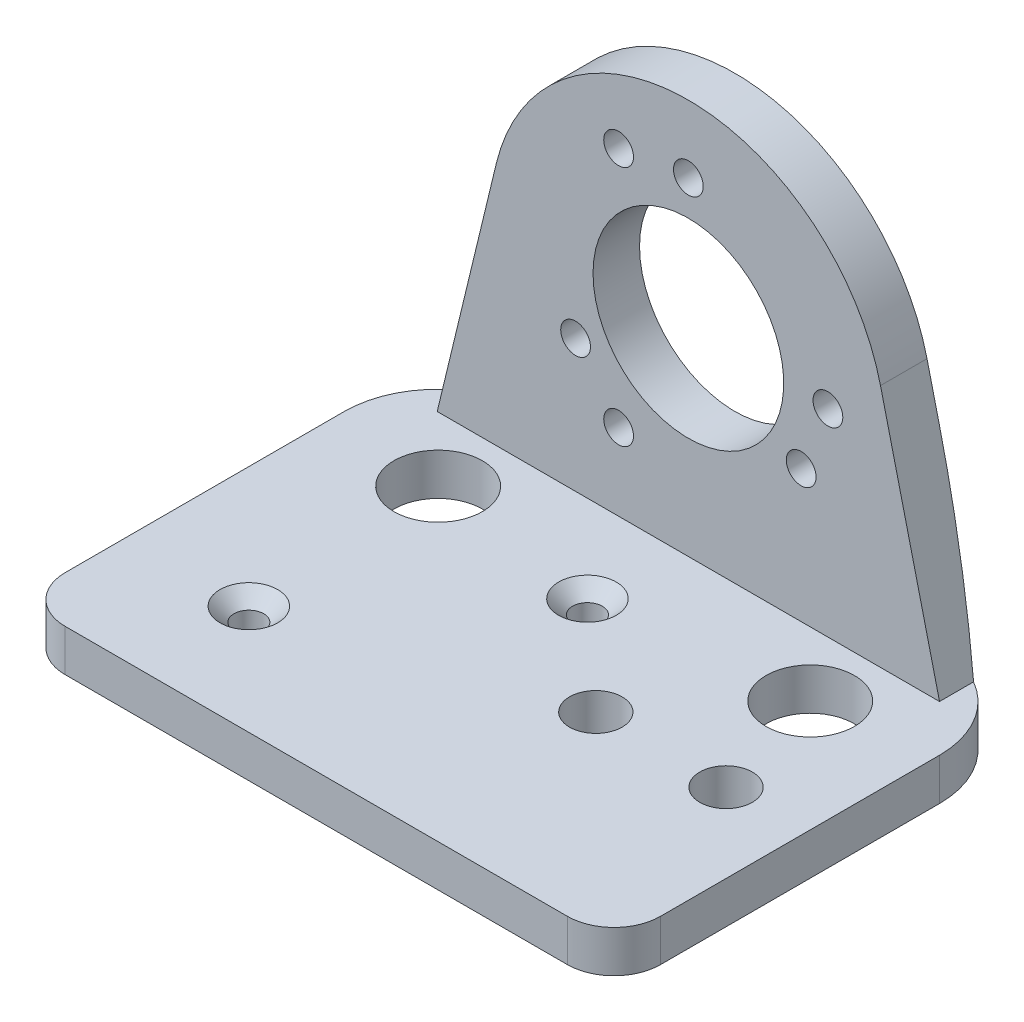
SolidWorks part; units mm, degrees
ref_plane "Front Plane" through (0, 0, 0) normal (0, 0, 1) x (1, 0, 0)
ref_plane "Top Plane" through (0, 0, 0) normal (0, 1, 0) x (1, 0, 0)
ref_plane "Right Plane" through (0, 0, 0) normal (1, 0, 0) x (0, 0, -1)
sketch "Sketch1" plane through (0, 0, 0) normal (0, 1, 0) x (1, 0, 0)
  line L0 (6.875, -1.95) -> (26.125, -1.95) construction
  line L1 (12.125, -1.95) -> (20.875, -1.95) construction
  line L2 (-32, -22.5) -> (32, -22.5)
  line L3 (32, -22.5) -> (32, 22.5)
  line L6 (-32, -22.5) -> (-32, 22.5)
  line L7 (-32, 22.5) -> (32, 22.5)
  line L9 (-32, 22.5) -> (32, -22.5) construction
  line L10 (32, 22.5) -> (-32, -22.5) construction
  line L11 (-20, 10.6) -> (0, 0) construction
  line L12 (0, 0) -> (20, 10.6) construction
  circle A0 centre (9.5, -1.95) radius 2.625 construction
  circle A1 centre (23.5, -1.95) radius 2.625 construction
  circle A2 centre (-1.5, 8.15) radius 1.6
  circle A3 centre (-19, -10.75) radius 1.6
  circle A4 centre (9.5, -1.95) radius 1.6 construction
  circle A5 centre (23.5, -1.95) radius 1.6 construction
  circle A7 centre (9.5, -1.95) radius 2.825
  circle A8 centre (23.5, -1.95) radius 2.825
  circle A9 centre (-20, 10.6) radius 4.75
  circle A10 centre (20, 10.6) radius 4.75
  point P19 (0, 0)
  dimension "D15" = 9.5
  dimension "D1" = 19.25
  dimension "D2" = 8.75
  dimension "D3" = 17.5
  dimension "D4" = 18.9
  dimension "D5" = 10.1
  dimension "D6" = 11
  dimension "D14" = 0.2
  dimension "D10" = 64
  dimension "D11" = 45
  dimension "D7" = 9.5
  dimension "D9" = 1.95
  dimension "D12" = 40
  dimension "D13" = 10.6
extrude "Boss-Extrude1" add sketch "Sketch1" against normal blind 4.5
chamfer "Chamfer1" distance 1.5 angle 45 2 edges at (-19, 0, 12.35) (-1.5, 0, -6.55)
sketch "Sketch2" plane through (0, 0, 0) normal (0, 0, 1) x (1, 0, 0)
  line L0 (-32, 0) -> (32, 0) construction
  line L1 (-27, 0) -> (-20.6549, 26.2438)
  line L2 (27, 0) -> (20.6549, 26.2438)
  line L3 (-27, 0) -> (-27, -4.5)
  line L4 (-27, -4.5) -> (27, -4.5)
  line L5 (27, -4.5) -> (27, 0)
  line L6 (-7.5, 34.2404) -> (0, 21.25) construction
  line L7 (0, 21.25) -> (0, 35.25) construction
  line L8 (-32, -4.5) -> (32, -4.5) construction
  line L9 (-32, -4.5) -> (-32, 0) construction
  line L10 (32, -4.5) -> (32, 0) construction
  circle A0 centre (0, 21.25) radius 19.25 construction
  arc A1 (20.6549, 26.2438) -> (-20.6549, 26.2438) centre (0, 21.25) ccw
  circle A2 centre (0, 21.25) radius 10.25
  circle A3 centre (0, 21.25) radius 15 construction
  circle A4 centre (0, 21.25) radius 14 construction
  circle A5 centre (0, 35.25) radius 1.6
  circle A6 centre (-7.5, 34.2404) radius 1.6
  circle A7 centre (12.1244, 14.25) radius 1.6
  circle A8 centre (15, 21.25) radius 1.6
  circle A9 centre (-12.1244, 14.25) radius 1.6
  circle A10 centre (-7.5, 8.2596) radius 1.6
  point P34 (0, 21.25)
  dimension "D1" = 38.5
  dimension "D3" = 20.5
  dimension "D4" = 28
  dimension "D5" = 30
  dimension "D7" = 3.2
  dimension "D2" = 2
  dimension "D6" = 30
  dimension "D9" = 5
  dimension "D10" = 5
extrude "Boss-Extrude2" add sketch "Sketch2" along normal blind 5 from surface starting at face at (0, -2.25, -22.5)
fillet "Fillet1" radius 5 2 edges at (32, -2.25, 22.5) (-32, -2.25, 22.5)
fillet "Fillet2" radius 10 2 edges at (32, -2.25, -22.5) (-32, -2.25, -22.5)
equation "\"m3 hole\"= 3.2"
equation "\"m4 hole\"= 4.2"
equation "\"m5 hole\"= 5.2"
equation "\"m6 hole\"= 6.2"
equation "\"m8 hole\"= 8.2"
equation "\"m3 tapped\"= 2.5"
equation "\"m4 tapped\"= 3.3"
equation "\"m5 tapped\"= 4.2"
equation "\"m6 tapped\"= 5"
equation "\"m8 tapped\"= 6.8"
equation "\"D8@Sketch1\"=\"m3 hole\""
equation "\"D7@Sketch2\"=\"m3 hole\""
